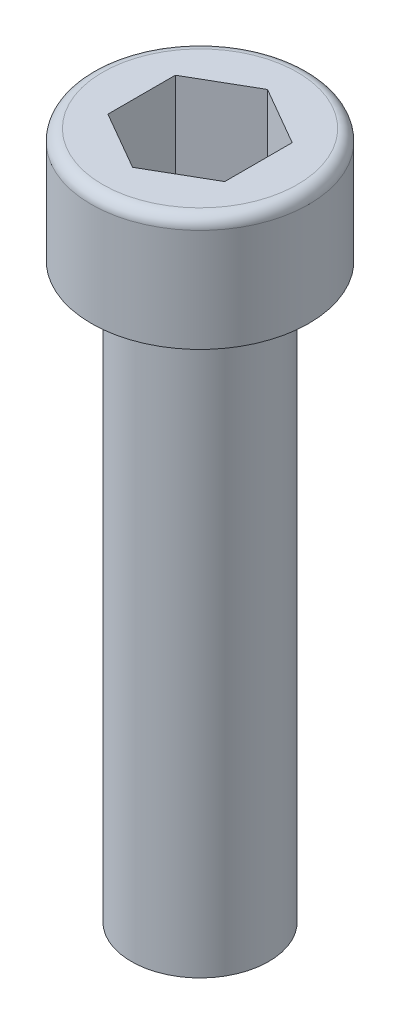
SolidWorks part; units mm, degrees
ref_plane "Front Plane" through (0, 0, 0) normal (0, 0, 1) x (1, 0, 0)
ref_plane "Top Plane" through (0, 0, 0) normal (0, 1, 0) x (1, 0, 0)
ref_plane "Right Plane" through (0, 0, 0) normal (1, 0, 0) x (0, 0, -1)
sketch "Sketch1" plane through (0, 0, 0) normal (0, 1, 0) x (1, 0, 0)
  circle A0 centre (0, 0) radius 4.75
  dimension "D1" = 9.5
extrude "Boss-Extrude1" add sketch "Sketch1" along normal blind 5
sketch "Sketch2" plane through (0, 0, 0) normal (0, -1, 0) x (1, 0, 0)
  circle A0 centre (0, 0) radius 3
  dimension "D1" = 6
extrude "Boss-Extrude2" add sketch "Sketch2" along normal blind 25
fillet "Fillet1" radius 0.5 1 edges at (0, 5, 4.75)
sketch "Sketch3" plane through (0, 5, 0) normal (0, 1, 0) x (1, 0, 0)
  line L5 (0, 2.9445) -> (-2.55, 1.4722)
  line L6 (-2.55, 1.4722) -> (-2.55, -1.4722)
  line L7 (-2.55, -1.4722) -> (0, -2.9445)
  line L8 (0, -2.9445) -> (2.55, -1.4722)
  line L9 (2.55, -1.4722) -> (2.55, 1.4722)
  line L10 (2.55, 1.4722) -> (0, 2.9445)
  circle A0 centre (0, 0) radius 2.55 construction
  dimension "D1" = 5.1
extrude "Cut-Extrude1" cut sketch "Sketch3" against normal blind 4
